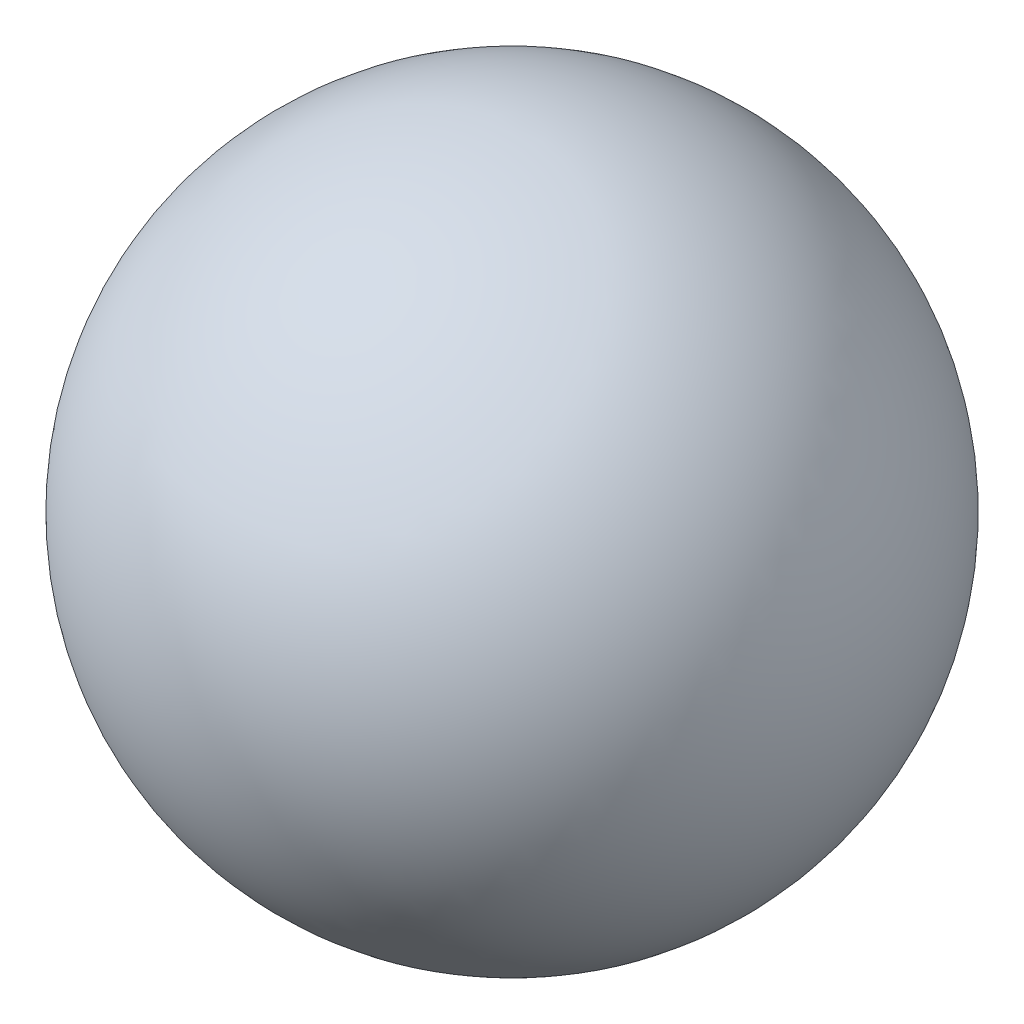
SolidWorks part; units mm, degrees
ref_plane "前视基准面" through (0, 0, 0) normal (0, 0, 1) x (1, 0, 0)
ref_plane "上视基准面" through (0, 0, 0) normal (0, 1, 0) x (1, 0, 0)
ref_plane "右视基准面" through (0, 0, 0) normal (1, 0, 0) x (0, 0, -1)
sketch "草图1" plane through (0, 0, 0) normal (0, 0, 1) x (1, 0, 0)
  line L0 (0, 17.311) -> (0, -16.7431) construction
  line L1 (0, 15) -> (0, -15)
  arc A0 (0, -15) -> (0, 15) centre (0, 0) ccw
  dimension "D1" = 30
revolve "旋转3" add sketch "草图1" angle 360 about L0
